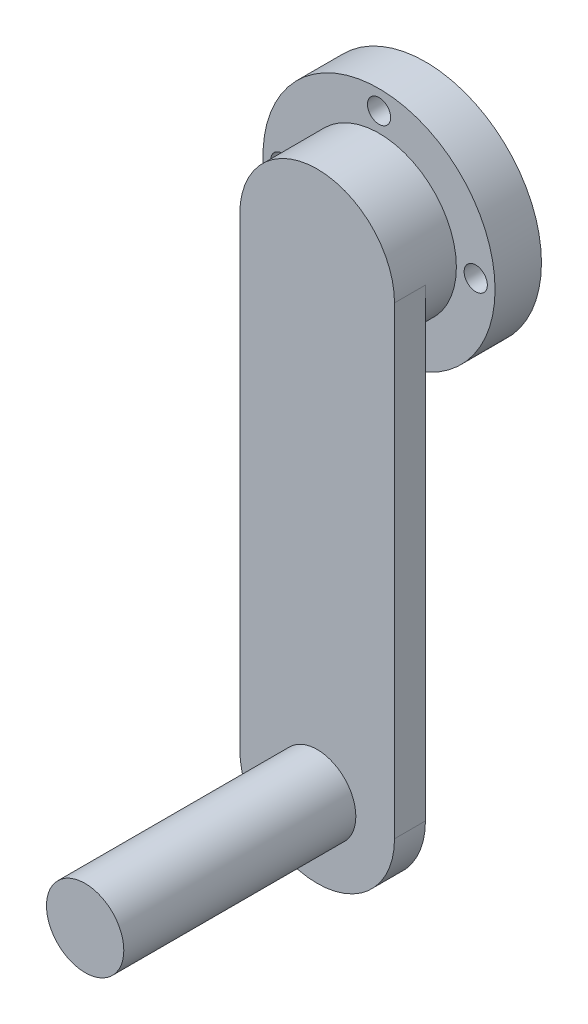
SolidWorks part; units mm, degrees
ref_plane "Front Plane" through (0, 0, 0) normal (0, 0, 1) x (1, 0, 0)
ref_plane "Top Plane" through (0, 0, 0) normal (0, 1, 0) x (1, 0, 0)
ref_plane "Right Plane" through (0, 0, 0) normal (1, 0, 0) x (0, 0, -1)
sketch "Sketch1" plane through (0, 0, 0) normal (0, 0, 1) x (1, 0, 0)
  circle A0 centre (0, 0) radius 15
  circle A2 centre (0, 12.5) radius 1.5
  circle A3 centre (12.5, 0) radius 1.5
  circle A4 centre (0, -12.5) radius 1.5
  circle A5 centre (-12.5, 0) radius 1.5
  point P14 (0, 0)
  dimension "D1" = 30
  dimension "D2" = 3
  dimension "D3" = 12.5
  dimension "D4" = 4
extrude "Boss-Extrude1" add sketch "Sketch1" along normal blind 6
sketch "Sketch2" plane through (0, 0, 6) normal (0, 0, 1) x (1, 0, 0)
  circle A0 centre (0, 0) radius 10
  dimension "D1" = 20
extrude "Boss-Extrude2" add sketch "Sketch2" along normal blind 4
sketch "Sketch4" plane through (0, 0, 10) normal (0, 0, 1) x (1, 0, 0)
  line L0 (0, -60) -> (0, 0) construction
  line L1 (-10, -60) -> (-10, 0)
  line L2 (10, -60) -> (10, 0)
  arc A0 (-10, -60) -> (10, -60) centre (0, -60) ccw
  arc A1 (10, 0) -> (-10, 0) centre (0, 0) ccw
  point P3 (0, -30)
  dimension "D1" = 10
  dimension "D2" = 60
extrude "Boss-Extrude3" add sketch "Sketch4" along normal blind 4
sketch "Sketch5" plane through (0, 0, 14) normal (0, 0, 1) x (1, 0, 0)
  circle A0 centre (0, -60) radius 5
  dimension "D1" = 10
extrude "Boss-Extrude4" add sketch "Sketch5" along normal blind 30
